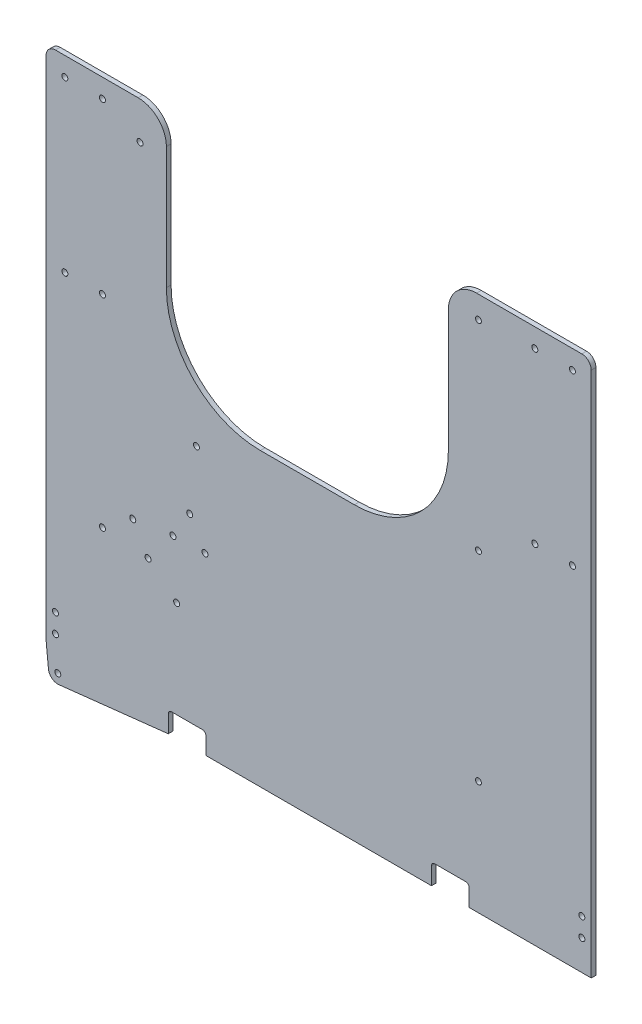
SolidWorks part; units mm, degrees
ref_plane "Front Plane" through (0, 0, 0) normal (0, 0, 1) x (1, 0, 0)
ref_plane "Top Plane" through (0, 0, 0) normal (0, 1, 0) x (1, 0, 0)
ref_plane "Right Plane" through (0, 0, 0) normal (1, 0, 0) x (0, 0, -1)
sketch "Sketch1" plane through (0, 0, 0) normal (0, 0, 1) x (1, 0, 0)
  line L0 (82.55, -20.32) -> (82.55, -6.35)
  line L2 (0, 0) -> (0, 341.63)
  line L3 (0, 341.63) -> (368.3, 341.63)
  line L4 (368.3, -20.32) -> (368.3, 341.63)
  line L5 (82.55, -6.35) -> (107.95, -6.35)
  line L6 (107.95, -6.35) -> (107.95, -20.32)
  line L7 (107.95, -20.32) -> (260.35, -20.32)
  line L8 (260.35, -20.32) -> (260.35, -6.35)
  line L9 (260.35, -6.35) -> (285.75, -6.35)
  line L10 (285.75, -6.35) -> (285.75, -20.32)
  line L11 (285.75, -20.32) -> (368.3, -20.32)
  line L12 (361.95, 12.7) -> (368.3, 12.7) construction
  line L13 (0, 0) -> (6.35, 0) construction
  line L14 (0.0315, -6.9818) -> (1.619, -22.8568)
  line L15 (8.6391, -28.5361) -> (82.55, -20.32)
  line L16 (0, 0) -> (0, -6.35)
  line L17 (85.725, 97.155) -> (82.9754, 95.5675) construction
  line L18 (97.0634, 115.6163) -> (58.5686, 93.3913) construction
  line L19 (97.0634, 115.6163) -> (107.3822, 97.7437) construction
  line L20 (58.5686, 93.3913) -> (68.8873, 75.5187) construction
  line L21 (107.3822, 97.7437) -> (68.8873, 75.5187) construction
  line L22 (97.0634, 115.6163) -> (68.8873, 75.5187) construction
  line L23 (58.5686, 93.3913) -> (107.3822, 97.7437) construction
  line L24 (7.9375, -22.225) -> (88.2169, 59.1366) construction
  line L25 (292.1, 56.63) -> (292.1, 191.63) construction
  line L26 (292.1, 191.63) -> (292.1, 326.63) construction
  line L27 (355.6, 328.93) -> (330.2, 328.93) construction
  line L28 (330.2, 328.93) -> (330.2, 214.63) construction
  line L29 (330.2, 214.63) -> (355.6, 214.63) construction
  line L30 (355.6, 214.63) -> (355.6, 328.93) construction
  line L31 (184.15, 341.63) -> (184.15, 269.4703) construction
  line L32 (12.7, 328.93) -> (38.1, 328.93) construction
  line L33 (38.1, 328.93) -> (38.1, 214.63) construction
  line L34 (12.7, 214.63) -> (12.7, 328.93) construction
  line L35 (38.1, 214.63) -> (12.7, 214.63) construction
  line L36 (81.28, 341.63) -> (81.28, 176.53)
  line L37 (81.28, 176.53) -> (271.78, 176.53)
  line L38 (271.78, 176.53) -> (271.78, 341.63)
  circle A0 centre (6.35, 0) radius 2.032
  circle A1 centre (6.35, 12.7) radius 2.032
  circle A2 centre (361.95, 0) radius 2.032
  circle A3 centre (361.95, 12.7) radius 2.032
  arc A5 (1.619, -22.8568) -> (8.6391, -28.5361) centre (7.9375, -22.225) ccw
  circle A6 centre (7.9375, -22.225) radius 2.032
  arc A7 (0, -6.35) -> (0.0315, -6.9818) centre (6.35, -6.35) ccw
  circle A8 centre (38.1, 78.105) radius 2.032
  circle A9 centre (85.725, 97.155) radius 2.032
  circle A10 centre (58.5686, 93.3913) radius 2.032
  circle A11 centre (68.8873, 75.5187) radius 2.032
  circle A12 centre (107.3822, 97.7437) radius 2.032
  circle A13 centre (97.0634, 115.6163) radius 2.032
  circle A14 centre (88.2169, 59.1366) radius 2.032
  circle A15 centre (292.1, 56.63) radius 2
  circle A16 centre (292.1, 191.63) radius 2
  circle A17 centre (292.1, 326.63) radius 2
  circle A18 centre (63.5, 316.23) radius 2.032
  circle A19 centre (101.6, 157.48) radius 2.032
  circle A20 centre (355.6, 328.93) radius 2.032
  circle A21 centre (330.2, 328.93) radius 2.032
  circle A22 centre (355.6, 214.63) radius 2.032
  circle A23 centre (330.2, 214.63) radius 2.032
  circle A24 centre (12.7, 328.93) radius 2.032
  circle A25 centre (38.1, 328.93) radius 2.032
  circle A26 centre (12.7, 214.63) radius 2.032
  circle A27 centre (38.1, 214.63) radius 2.032
  dimension "D6" = 4.064
  dimension "D10" = 6.35
  dimension "D11" = 4.064
  dimension "D17" = 38.1
  dimension "D27" = 4
  dimension "D31" = 4.064
  dimension "D32" = 25.4
  dimension "D36" = 4.064
  dimension "D2" = 361.95
  dimension "D3" = 13.97
  dimension "D4" = 25.4
  dimension "D5" = 152.4
  dimension "D7" = 12.7
  dimension "D8" = 6.35
  dimension "D9" = 20.32
  dimension "D12" = 22.225
  dimension "D13" = 1.5875
  dimension "D14" = 82.55
  dimension "D15" = 368.3
  dimension "D16" = 6.35
  dimension "D18" = 98.425
  dimension "D19" = 47.625
  dimension "D20" = 19.05
  dimension "D21" = 3.175
  dimension "D22" = 60
  dimension "D23" = 20.6375
  dimension "D24" = 44.45
  dimension "D25" = 38.1
  dimension "D26" = 114.3
  dimension "D28" = 135
  dimension "D29" = 15
  dimension "D30" = 76.2
  dimension "D33" = 63.5
  dimension "D34" = 184.15
  dimension "D35" = 101.6
  dimension "D37" = 114.3
  dimension "D38" = 25.4
  dimension "D39" = 12.7
  dimension "D40" = 12.7
  dimension "D41" = 190.5
  dimension "D42" = 81.28
  dimension "D43" = 165.1
extrude "Boss-Extrude1" add sketch "Sketch1" along normal blind 3.175 contours L16 A7 L14 A5 L15 L0 L5 L6 L7 L8 L9 L10 L11 L4 L3 L38 L37 L36 L2 A26 A24 A23 A22 A21 A20 A19 A18 A17 A16 A15 A14 A13 A12 A11 region at (186.0991, 130.6728, 0)
fillet "Fillet1" radius 2.286 4 edges at (285.75, -6.35, 1.5875) (107.95, -6.35, 1.5875) (260.35, -6.35, 1.5875) (82.55, -6.35, 1.5875)
fillet "Fillet2" radius 6.35 2 edges at (368.3, 341.63, 1.5875) (0, 341.63, 1.5875)
fillet "Fillet3" radius 19.05 2 edges at (271.78, 341.63, 1.5875) (81.28, 341.63, 1.5875)
fillet "Fillet4" radius 63.5 2 edges at (271.78, 176.53, 1.5875) (81.28, 176.53, 1.5875)
